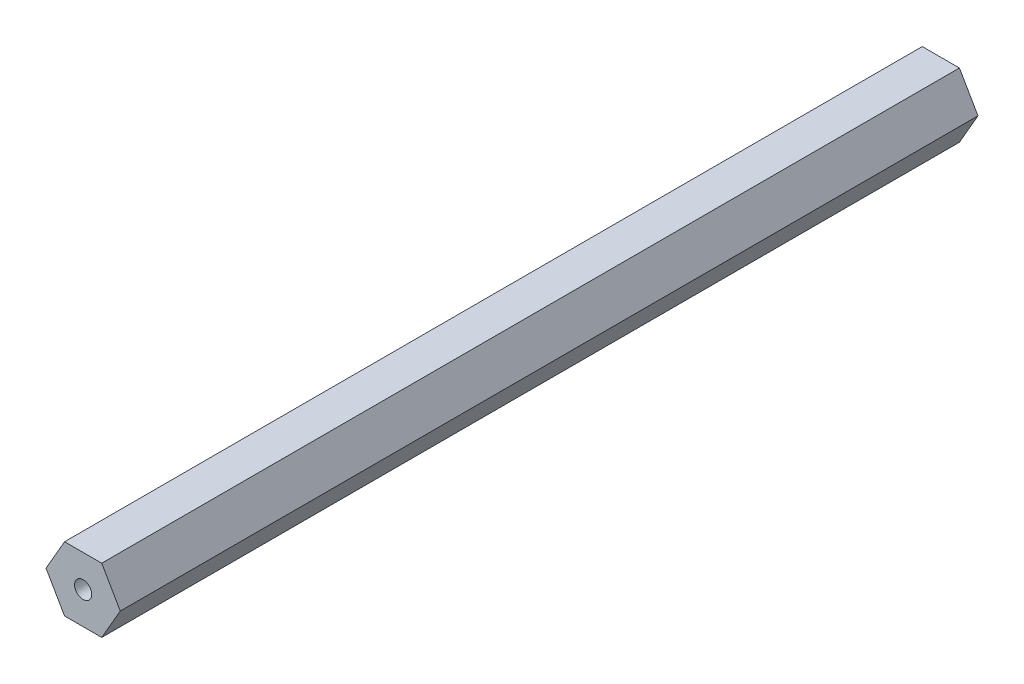
SolidWorks part; units mm, degrees
ref_plane "Front Plane" through (0, 0, 0) normal (0, 0, 1) x (1, 0, 0)
ref_plane "Top Plane" through (0, 0, 0) normal (0, 1, 0) x (1, 0, 0)
ref_plane "Right Plane" through (0, 0, 0) normal (1, 0, 0) x (0, 0, -1)
sketch "Sketch1" plane through (0, 0, 0) normal (0, 0, 1) x (1, 0, 0)
  line L1 (16.408, -2.6676) -> (13.6584, 2.0949)
  line L2 (13.6584, 2.0949) -> (8.1591, 2.0949)
  line L3 (8.1591, 2.0949) -> (5.4095, -2.6676)
  line L4 (5.4095, -2.6676) -> (8.1591, -7.4301)
  line L5 (8.1591, -7.4301) -> (13.6584, -7.4301)
  line L6 (13.6584, -7.4301) -> (16.408, -2.6676)
  circle A0 centre (10.9088, -2.6676) radius 4.7625 construction
  circle A1 centre (10.9088, -2.6676) radius 1.27
  dimension "D1" = 9.525
extrude "Boss-Extrude1" add sketch "Sketch1" along normal blind 127
